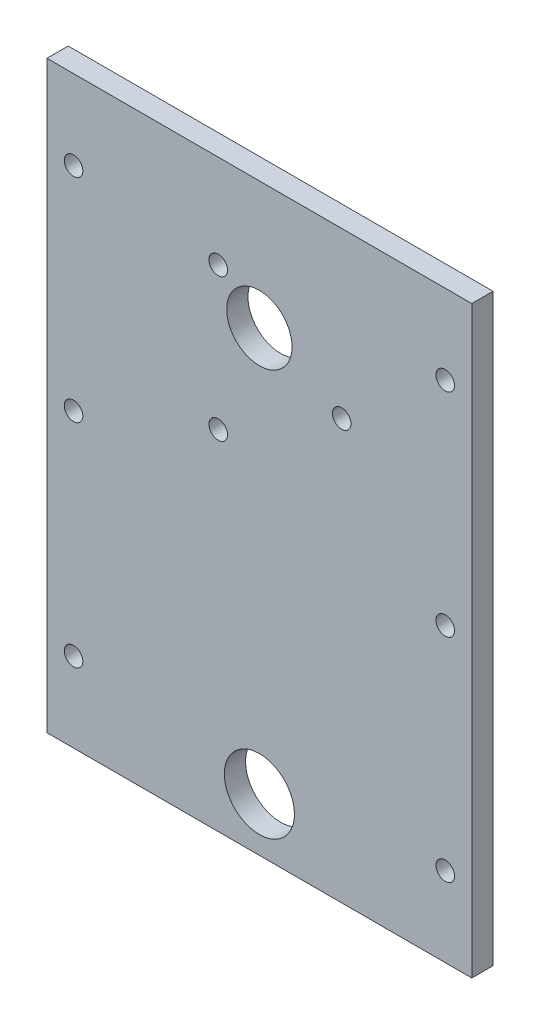
SolidWorks part; units mm, degrees
ref_plane "正面" through (0, 0, 0) normal (0, 0, 1) x (1, 0, 0)
ref_plane "平面" through (0, 0, 0) normal (0, 1, 0) x (1, 0, 0)
ref_plane "右側面" through (0, 0, 0) normal (1, 0, 0) x (0, 0, -1)
sketch "ｽｹｯﾁ1" plane through (0, 0, 0) normal (0, 0, 1) x (1, 0, 0)
  line L0 (40, 0) -> (40, 10)
  line L1 (0, 0) -> (80, 0)
  line L2 (0, 0) -> (0, 110)
  line L3 (0, 110) -> (80, 110)
  line L4 (80, 0) -> (80, 110)
  line L5 (0, 110) -> (5, 110)
  line L6 (0, 110) -> (0, 95)
  line L7 (0, 95) -> (5, 95)
  line L8 (5, 110) -> (5, 95)
  line L9 (80, 0) -> (75, 0)
  line L10 (80, 0) -> (80, 15)
  line L11 (80, 15) -> (75, 15)
  line L12 (75, 0) -> (75, 15)
  line L13 (40, 10) -> (40, 79)
  line L14 (40, 79) -> (55.5, 79)
  line L15 (40, 79) -> (32.25, 92.4234)
  line L16 (40, 79) -> (32.25, 65.5766)
  circle A0 centre (5, 95) radius 1.75
  circle A1 centre (5, 15) radius 1.75
  circle A2 centre (75, 95) radius 1.75
  circle A3 centre (75, 15) radius 1.75
  circle A4 centre (40, 10) radius 6.6
  circle A6 centre (55.5, 79) radius 1.75
  circle A7 centre (32.25, 92.4234) radius 1.75
  circle A8 centre (32.25, 65.5766) radius 1.75
  circle A9 centre (75, 55) radius 1.75
  circle A10 centre (5, 55) radius 1.75
  circle A11 centre (40, 86) radius 6.15
  point P8 (5, 102.5)
  point P32 (75, 105)
  dimension "D7" = 10
  dimension "D8" = 13.2
  dimension "D13" = 7
  dimension "D15" = 40
  dimension "D14" = 15
  dimension "D20" = 15
  dimension "D18" = 55
  dimension "D17" = 55
  dimension "D1" = 80
  dimension "D2" = 110
  dimension "D3" = 15
  dimension "D4" = 5
  dimension "D5" = 15
  dimension "D6" = 5
  dimension "D9" = 69
  dimension "D10" = 15.5
  dimension "D11" = 120
  dimension "D12" = 120
  dimension "D16" = 5
  dimension "D19" = 5
extrude "ﾎﾞｽ - 押し出し1" add sketch "ｽｹｯﾁ1" along normal blind 4 contours A8 A7 A6 A11 A4 L1 L12 A3 L11 L4 L3 L8 A0 L7 L2 A2 A1 | A0 L8 L3 L2 L7 | A3 L12 L1 L4 L11 region at (20, 1.3601, 0) region at (77.5582, 7.2761, 0) region at (2.4418, 102.7239, 0)
